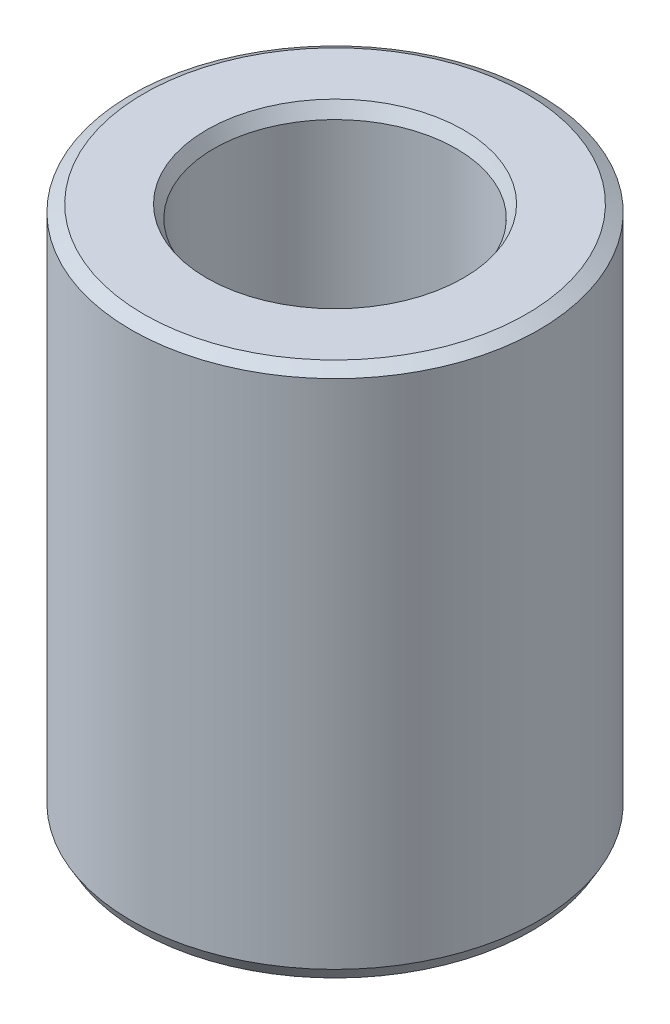
SolidWorks part; units mm, degrees
ref_plane "Front Plane" through (0, 0, 0) normal (0, 0, 1) x (1, 0, 0)
ref_plane "Top Plane" through (0, 0, 0) normal (0, 1, 0) x (1, 0, 0)
ref_plane "Right Plane" through (0, 0, 0) normal (1, 0, 0) x (0, 0, -1)
sketch "Sketch1" plane through (0, 0, 0) normal (0, 1, 0) x (1, 0, 0)
  circle A0 centre (0, 0) radius 60
  dimension "SLEEVE_OD" = 120
extrude "Boss-Extrude1" add sketch "Sketch1" along normal blind 156.4822
sketch "Sketch2" plane through (0, 0, 0) normal (0, 1, 0) x (1, 0, 0)
  circle A0 centre (0, 0) radius 35.6636
  dimension "BORE_D" = 71.3273
extrude "Cut-Extrude1" cut sketch "Sketch2" along normal through all
chamfer "Chamfer1" distance 2.1387 angle 60 4 edges at (0, 156.4822, 35.6636) (0, 0, 35.6636) (0, 0, 60) (0, 156.4822, 60) first distance on face at (0, 156.4822, 35.6636) first distance on face at (0, 0, 35.6636) first distance on face at (0, 156.4822, 60)
